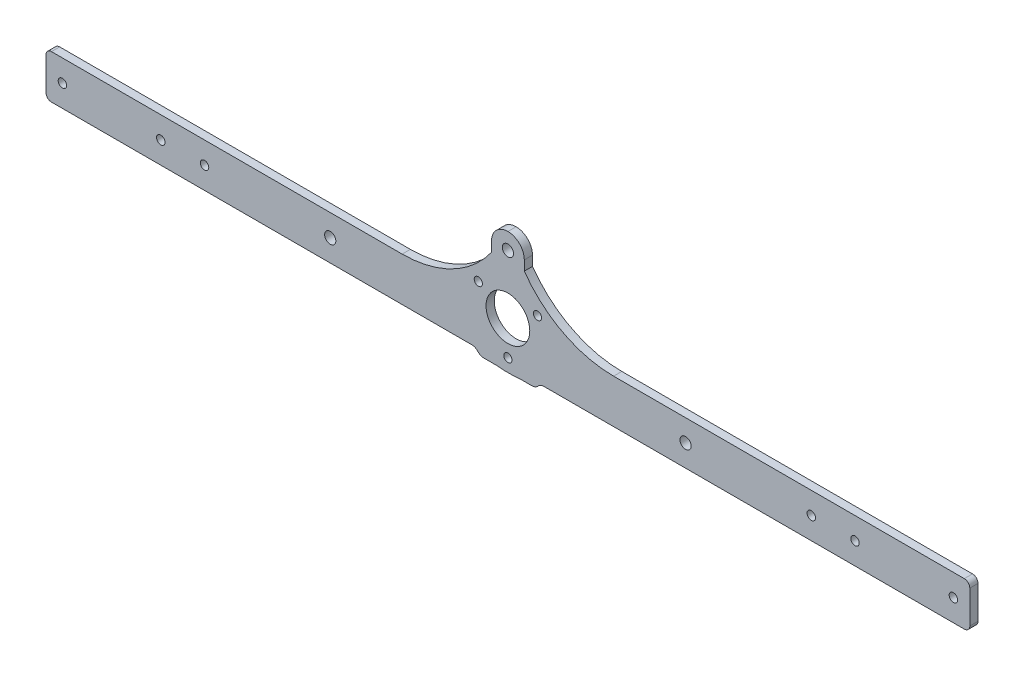
SolidWorks part; units mm, degrees
ref_plane "Спереди" through (0, 0, 0) normal (0, 0, 1) x (1, 0, 0)
ref_plane "Сверху" through (0, 0, 0) normal (0, 1, 0) x (1, 0, 0)
ref_plane "Справа" through (0, 0, 0) normal (1, 0, 0) x (0, 0, -1)
sketch "Эскиз Петрушки" plane through (0, 0, 0) normal (0, 0, 1) x (1, 0, 0)
  line L0 (0, 0) -> (0, -24) construction
  line L1 (0, 0) -> (145, -7) construction
  line L2 (163, -7) -> (111, -7) construction
  line L4 (145, -93) -> (-145, -93) construction
  line L6 (145, -7) -> (145, -93) construction
  line L8 (-145, -7) -> (-145, -93) construction
  line L9 (-145, -93) -> (145, -93) construction
  line L10 (-163, -7) -> (-111, -7) construction
  line L11 (0, 0) -> (-145, -7) construction
  circle A0 centre (0, 21.5) radius 2.05
  circle A1 centre (145, -93) radius 57.5 construction
  circle A3 centre (163, -7) radius 1.55
  circle A4 centre (127, -7) radius 1.55
  circle A5 centre (111, -7) radius 1.55
  circle A6 centre (-145, -93) radius 57.5 construction
  circle A7 centre (-111, -7) radius 1.55
  circle A8 centre (-127, -7) radius 1.55
  circle A9 centre (-163, -7) radius 1.55
  dimension "D2" = 4.1
  dimension "D3" = 7
  dimension "D4" = 3.1
  dimension "D5" = 145
  dimension "D10" = 115
  dimension "D11" = 21.5
  dimension "D6" = 86
  dimension "D7" = 18
  dimension "D8" = 18
  dimension "D9" = 34
sketch "Эскиз8" plane through (0, 0, 0) normal (0, 0, 1) x (1, 0, 0)
  line L1 (38.6766, 1) -> (169, 1)
  line L2 (169, 1) -> (169, -15)
  line L3 (169, -15) -> (90, -15)
  line L5 (-15.2242, 4.7143) -> (-13.046, -3.4714) construction
  line L10 (105, 1) -> (105, -15) construction
  line L12 (-11.6948, 10.8274) -> (-3.5167, 13.0339) construction
  line L13 (3.5294, -15.5417) -> (9.5294, -9.5625) construction
  line L14 (-3.5294, -15.5417) -> (-9.5294, -9.5625) construction
  line L15 (0, -12.5) -> (0, 0) construction
  line L17 (0, 0) -> (-10.3923, 6) construction
  line L18 (11.6948, 10.8274) -> (3.5167, 13.0339) construction
  line L19 (0, 0) -> (10.3923, 6) construction
  line L20 (6, 27.5) -> (-6, 27.5)
  line L23 (15.2242, 4.7143) -> (13.046, -3.4714) construction
  line L26 (6, 17.9296) -> (6, 27.5)
  line L29 (-10, -17) -> (-12, -15)
  line L30 (6, 17.9296) -> (6, 12.3639) construction
  line L31 (-6, 17.9296) -> (-6, 27.5)
  line L34 (-169, -15) -> (-90, -15)
  line L35 (-169, 1) -> (-169, -15)
  line L36 (-38.6766, 1) -> (-169, 1)
  line L37 (-90, -15) -> (-12, -15)
  line L39 (-10, -17) -> (-4.2308, -17)
  line L40 (10, -17) -> (12, -15)
  line L41 (12, -15) -> (90, -15)
  line L42 (4.2308, -17) -> (10, -17)
  circle A2 centre (0, 0) radius 8
  circle A3 centre (0, 0) radius 13.5 construction
  arc A4 (-11.6948, 10.8274) -> (-15.2242, 4.7143) centre (-10.3923, 6) ccw construction
  arc A5 (3.5167, 13.0339) -> (-3.5167, 13.0339) centre (0, 0) ccw construction
  arc A6 (-3.5294, -15.5417) -> (3.5294, -15.5417) centre (0, -12) ccw construction
  arc A7 (15.2242, 4.7143) -> (11.6948, 10.8274) centre (10.3923, 6) ccw construction
  arc A8 (9.5294, -9.5625) -> (13.046, -3.4714) centre (0, 0) ccw construction
  arc A9 (-9.5294, -9.5625) -> (-13.046, -3.4714) centre (0, 0) cw construction
  circle A10 centre (0, 0) radius 12 construction
  circle A11 centre (0, -12.5) radius 1.5
  circle A15 centre (163, -7) radius 1.55
  circle A16 centre (111, -7) radius 1.55
  circle A17 centre (0, 21.5) radius 2.05
  circle A21 centre (127, -7) radius 1.55
  circle A22 centre (-10.8253, 6.25) radius 1.5
  circle A23 centre (10.8253, 6.25) radius 1.5
  circle A24 centre (0, 21.5) radius 2.05 construction
  circle A25 centre (127, -7) radius 1.55 construction
  circle A26 centre (111, -7) radius 1.55 construction
  circle A27 centre (163, -7) radius 1.55 construction
  arc A28 (6, 17.9296) -> (38.6766, 1) centre (38.6766, 41) ccw
  arc A29 (-6, 17.9296) -> (-38.6766, 1) centre (-38.6766, 41) cw
  circle A30 centre (-127, -7) radius 1.55
  circle A31 centre (-111, -7) radius 1.55
  circle A32 centre (-163, -7) radius 1.55
  circle A33 centre (0, 0) radius 12.5 construction
  arc A34 (-4.2308, -17) -> (4.2308, -17) centre (0, 21.5) ccw
  point P6 (169, -7)
  point P25 (0, 27.5)
  point P49 (0, 0)
  point P53 (0, 0)
  point P70 (0, 0)
  dimension "D2" = 16
  dimension "D3" = 5
  dimension "D4" = 24
  dimension "D5" = 27
  dimension "D6" = 3
  dimension "D7" = 6
  dimension "D16" = 40
  dimension "D8" = 25
  dimension "D1" = 16
  dimension "D9" = 12
  dimension "D10" = 120
  dimension "D11" = 120
  dimension "D12" = 20
  dimension "D13" = 45
  dimension "D14" = 15
  dimension "D18" = 6
  dimension "D22" = 6
  dimension "D20" = 3
extrude "Арка Петрушки" add sketch "Эскиз8" along normal blind 3
fillet "Скругление27" radius 6 2 edges at (-6, 27.5, 1.5) (6, 27.5, 1.5)
fillet "Скругление28" [suppressed] radius 8
fillet "Скругление29" [suppressed] radius 100
fillet "Скругление30" radius 3 4 edges at (-10, -17, 1.5) (12, -15, 1.5) (-12, -15, 1.5) (10, -17, 1.5)
fillet "Скругление31" radius 2 4 edges at (169, -15, 1.5) (169, 1, 1.5) (-169, -15, 1.5) (-169, 1, 1.5)
sketch "Эскиз9" plane through (0, 0, 3) normal (0, 0, 1) x (1, 0, 0)
  line L0 (0, 0) -> (0, 27.5) construction
  line L1 (-65, 1) -> (-65, -15) construction
  line L2 (-38.6766, 1) -> (-167, 1) construction
  line L3 (-167, -15) -> (-13.2426, -15) construction
  circle A0 centre (-65, -7) radius 2.05
  circle A1 centre (0, 21.5) radius 2.05 construction
  circle A2 centre (65, -7) radius 2.05
  point P14 (-70.9865, -7)
  point P15 (0, 0)
  dimension "D1" = 65
extrude "Вырез-Вытянуть1" cut sketch "Эскиз9" against normal through all
